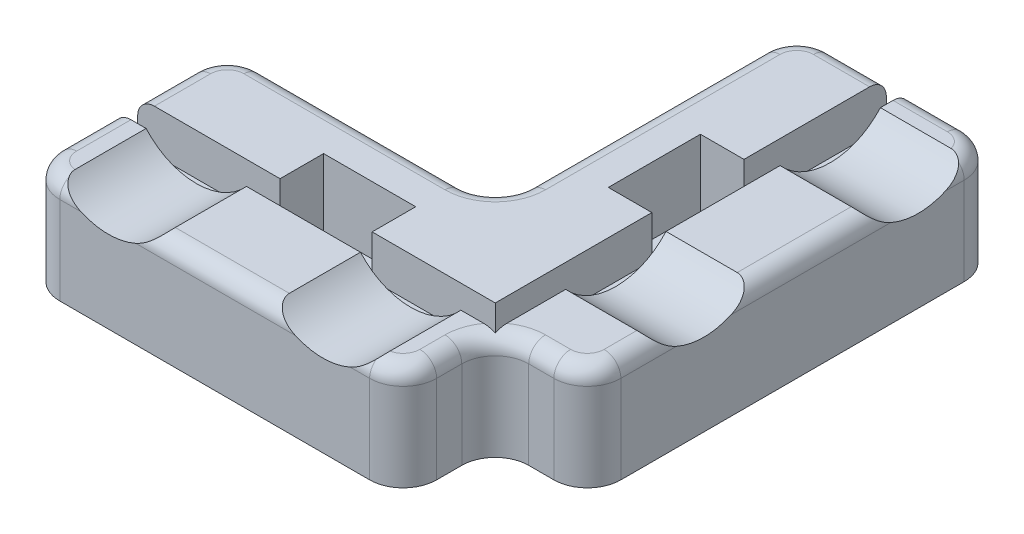
SolidWorks part; units mm, degrees
ref_plane "Спереди" through (0, 0, 0) normal (0, 0, 1) x (1, 0, 0)
ref_plane "Сверху" through (0, 0, 0) normal (0, 1, 0) x (1, 0, 0)
ref_plane "Справа" through (0, 0, 0) normal (1, 0, 0) x (0, 0, -1)
sketch "Эскиз1" plane through (0, 0, 0) normal (0, 1, 0) x (1, 0, 0)
  line L9 (4, 0) -> (41, 0)
  line L10 (0, 4) -> (0, 20)
  line L11 (4, 24) -> (28, 24)
  line L12 (45, 4) -> (45, 7)
  line L17 (36, 60) -> (52, 60)
  line L18 (32, 56) -> (32, 28)
  line L19 (49, 11) -> (52, 11)
  line L20 (56, 56) -> (56, 15)
  arc A0 (52, 11) -> (56, 15) centre (52, 15) ccw
  arc A1 (41, 0) -> (45, 4) centre (41, 4) ccw
  arc A2 (36, 60) -> (32, 56) centre (36, 56) ccw
  arc A3 (52, 60) -> (56, 56) centre (52, 56) cw
  arc A4 (0, 20) -> (4, 24) centre (4, 20) cw
  arc A5 (4, 0) -> (0, 4) centre (4, 4) cw
  arc A6 (49, 11) -> (45, 7) centre (49, 7) ccw
  arc A7 (28, 24) -> (32, 28) centre (28, 28) ccw
  point P5 (0, 0)
  point P11 (60.9464, 12.5443)
  point P15 (56, 11)
  point P18 (45, 0)
  point P23 (56, 60)
  point P26 (0, 24)
  point P30 (0, 0)
  dimension "D3" = 49
  dimension "D4" = 11
  dimension "D6" = 4
  dimension "D1" = 24
  dimension "D2" = 45
  dimension "D5" = 11
extrude "Тело" add sketch "Эскиз1" along normal blind 12.5
sketch "Эскиз6" plane through (0, 0, 0) normal (0, -1, 0) x (1, 0, 0)
  line L0 (4, -24) -> (28, -24) construction
  line L1 (32, -56) -> (32, -28) construction
  circle A0 centre (4, -4) radius 0.9
  circle A1 centre (41, -4) radius 0.9
  circle A2 centre (52, -15) radius 0.9
  circle A3 centre (4, -20) radius 0.9
  circle A4 centre (36, -56) radius 0.9
  circle A5 centre (52, -56) radius 0.9
  circle A6 centre (34, -22) radius 0.9
  dimension "D1" = 1.8
  dimension "D2" = 2
  dimension "D3" = 2
extrude "Крепеж" cut sketch "Эскиз6" against normal blind 7
fillet "Скругление1" radius 2 16 edges at (1.1716, 12.5, -1.1716) (0, 12.5, -12) (1.1716, 12.5, -22.8284) (16, 12.5, -24) (30.8284, 12.5, -25.1716) (32, 12.5, -42) (33.1716, 12.5, -58.8284) (44, 12.5, -60) (54.8284, 12.5, -58.8284) (56, 12.5, -35.5) (54.8284, 12.5, -12.1716) (50.5, 12.5, -11) (46.1716, 12.5, -9.8284) (45, 12.5, -5.5) (43.8284, 12.5, -1.1716) (22.5, 12.5, 0)
sketch "Эскиз7" plane through (0, 12.5, 0) normal (0, 1, 0) x (1, 0, 0)
  line L0 (4, 2) -> (41, 2) construction
  line L1 (17, 18.5) -> (28, 18.5)
  line L2 (17, 18.5) -> (17, 15.5)
  line L3 (17, 15.5) -> (28, 15.5)
  line L4 (28, 18.5) -> (28, 15.5)
  line L5 (56, 56) -> (56, 15) construction
  line L6 (37.5, 43) -> (40.5, 43)
  line L7 (37.5, 43) -> (37.5, 32)
  line L8 (37.5, 32) -> (40.5, 32)
  line L9 (40.5, 43) -> (40.5, 32)
  line L10 (52, 11) -> (49, 11) construction
  point P4 (17, 17)
  point P8 (22.5, 15.5)
  point P9 (22.5, 2)
  point P14 (39, 32)
  point P17 (40.5, 37.5)
  dimension "D1" = 3
  dimension "D2" = 11
  dimension "D3" = 17
  dimension "D4" = 17
  dimension "D5" = 26.5
extrude "Вырез-Вытянуть1" cut sketch "Эскиз7" against normal through all and the other way through all
sketch "Эскиз8" plane through (0, 12.5, 0) normal (0, 1, 0) x (1, 0, 0)
  line L0 (17, 18.5) -> (17, 15.5) construction
  line L1 (0, 13.3) -> (17, 13.3)
  line L2 (0, 13.3) -> (0, 10.5)
  line L3 (0, 10.5) -> (45.5, 10.5)
  line L6 (37.5, 32) -> (40.5, 32) construction
  line L7 (42.7, 60.5) -> (45.5, 60.5)
  line L8 (42.7, 60.5) -> (42.7, 43)
  line L10 (45.5, 60.5) -> (45.5, 10.5)
  line L11 (40.5, 32) -> (40.5, 43) construction
  line L12 (28, 15.5) -> (28, 18.5) construction
  line L14 (17, 13.3) -> (17, 15.5)
  line L15 (17, 15.5) -> (28, 15.5)
  line L16 (28, 13.3) -> (28, 15.5)
  line L17 (40.5, 43) -> (37.5, 43) construction
  line L18 (42.7, 43) -> (40.5, 43)
  line L20 (42.7, 32) -> (40.5, 32)
  line L21 (40.5, 43) -> (40.5, 32)
  line L22 (28, 13.3) -> (42.7, 13.3)
  line L23 (42.7, 32) -> (42.7, 13.3)
  line L24 (0, 4) -> (0, 20) construction
  point P3 (45.5, 10.6952)
  point P4 (17, 17)
  point P7 (39, 32)
  point P8 (40.5, 37.5)
  point P9 (17, 15.5)
  point P10 (28, 15.5)
  point P11 (0, 0)
  point P18 (0, 0)
  point P19 (45.5, 13.6553)
  point P22 (40.5, 37.5)
  point P23 (0, 0)
  point P36 (0, 8.45)
  point P39 (0, 0)
  dimension "D1" = 6.5
  dimension "D2" = 45.5
  dimension "D3" = 2.8
  dimension "D4" = 6.5
  dimension "D5" = 17.5
extrude "Вырез-Вытянуть2" cut sketch "Эскиз8" against normal offset from surface (5 mm away) 7.5 up to face at (22.5, 0, -17)
sketch "Эскиз9" plane through (0, 0, 0) normal (0, 0, 1) x (1, 0, 0)
  line L0 (4, 0) -> (41, 0) construction
  line L1 (45.5, 7.5) -> (0, 7.5) construction
  circle A0 centre (9.8, 17.8) radius 8
  circle A1 centre (35.4, 17.8) radius 8
  point P4 (0, 0)
  point P7 (22.5, 0)
  point P8 (35.3, 15.4423)
  dimension "D1" = 16
  dimension "D2" = 12.9
  dimension "D3" = 12.7
  dimension "D4" = 10.3
extrude "Вырез-Вытянуть3" cut sketch "Эскиз9" against normal up to surface (13.3 mm away) up to face at (7.1172, 10.1828, -13.3)
sketch "Эскиз10" plane through (56, 0, 0) normal (1, 0, 0) x (0, 0, -1)
  line L2 (43, 12.5) -> (32, 12.5) construction
  line L3 (60, 7.5) -> (10.5, 7.5) construction
  circle A0 centre (24.9, 17.8) radius 8
  circle A1 centre (50.5, 17.8) radius 8
  point P7 (37.5, 12.5)
  point P9 (0, 0)
  dimension "D1" = 16
  dimension "D2" = 12.6
  dimension "D3" = 13
  dimension "D4" = 10.3
extrude "Вырез-Вытянуть4" cut sketch "Эскиз10" against normal up to surface (13.3 mm away) up to face at (42.7, 10, -22.65)
